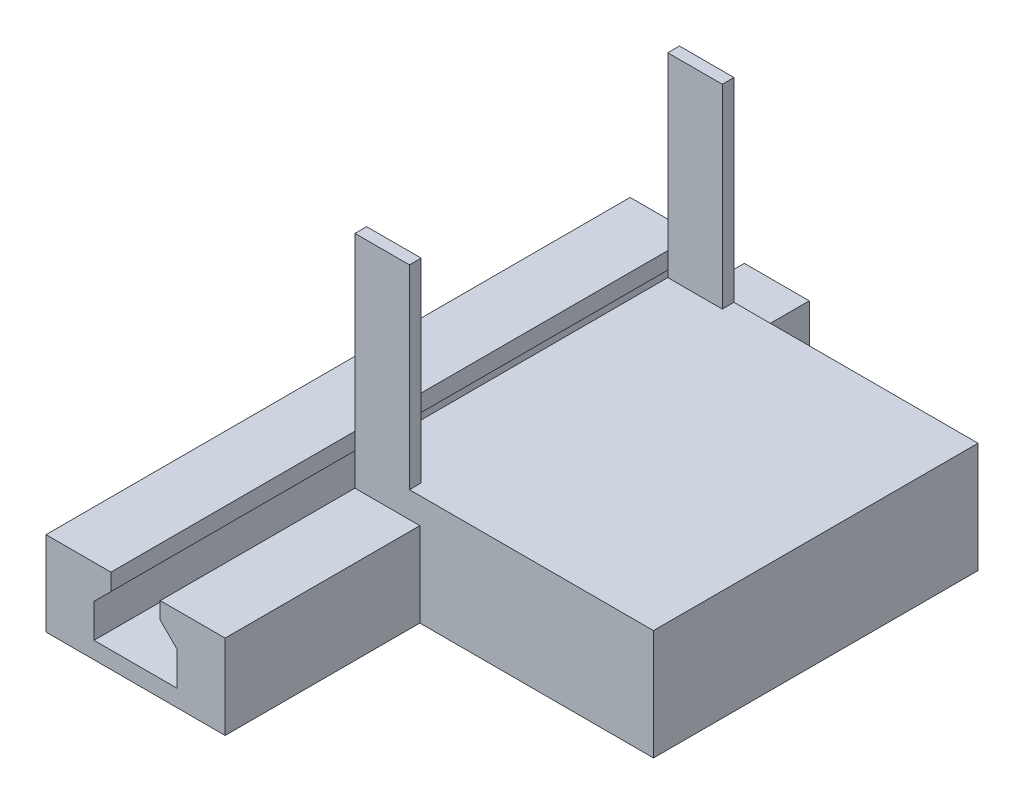
SolidWorks part; units mm, degrees
ref_plane "Plan de face" through (0, 0, 0) normal (0, 0, 1) x (1, 0, 0)
ref_plane "Plan de dessus" through (0, 0, 0) normal (0, 1, 0) x (1, 0, 0)
ref_plane "Plan de droite" through (0, 0, 0) normal (1, 0, 0) x (0, 0, -1)
sketch "Esquisse1" plane through (0, 0, 0) normal (0, 0, 1) x (1, 0, 0)
  line L0 (0, 0) -> (0, -5.2499) construction
  line L5 (0, 0) -> (0, 6.7252) construction
  line L6 (0, 0) -> (7.76, 0) construction
  line L7 (0, 0) -> (-6.4576, 0) construction
  line L8 (-3.2, 0) -> (3.2, 0)
  line L9 (-3.2, 0) -> (-3.2, 2.6)
  line L10 (3.2, 0) -> (3.2, 2.6)
  line L12 (-1.9, 5.2) -> (-1.9, 3.9)
  line L13 (1.9, 5.2) -> (1.9, 3.9)
  line L14 (-3.2, 2.6) -> (-1.9, 3.9)
  line L15 (1.9, 3.9) -> (3.2, 2.6)
  line L16 (-1.9, 5.2) -> (-6.9, 5.2)
  line L17 (-6.9, 5.2) -> (-6.9, -2.3)
  line L18 (-6.9, -2.3) -> (6.9, -2.3)
  line L19 (6.9, -2.3) -> (6.9, 5.2)
  line L20 (6.9, 5.2) -> (1.9, 5.2)
  point P10 (0, 0)
  point P15 (0, 5.2)
  dimension "D1" = 6.4
  dimension "D2" = 2.6
  dimension "D3" = 2.6
  dimension "D4" = 3.8
  dimension "D5" = 1.3
  dimension "D6" = 1.3
  dimension "D7" = 1.3
  dimension "D8" = 5
  dimension "D9" = 5
  dimension "D10" = 7.5
extrude "Boss.-Extru.1" add sketch "Esquisse1" along normal blind 45
sketch "Esquisse6" plane through (6.9, 0, 0) normal (1, 0, 0) x (0, 0, -1)
  line L0 (-45, -2.3) -> (0, -2.3) construction
  line L1 (-30, -2.3) -> (-5, -2.3)
  line L2 (-30, -2.3) -> (-30, 5.2)
  line L3 (-30, 5.2) -> (-5, 5.2)
  line L4 (-5, -2.3) -> (-5, 5.2)
  line L5 (-45, 5.2) -> (0, 5.2) construction
  line L6 (0, -2.3) -> (0, 5.2) construction
  dimension "D1" = 5
  dimension "D2" = 25
extrude "Boss.-Extru.6" add sketch "Esquisse6" along normal blind 18
sketch "Esquisse7" plane through (0, 5.2, 0) normal (0, 1, 0) x (1, 0, 0)
  line L0 (1.9, -45) -> (1.9, 0) construction
  line L1 (24.9, -30) -> (1.9, -30)
  line L2 (24.9, -30) -> (24.9, -5)
  line L3 (24.9, -5) -> (1.9, -5)
  line L4 (1.9, -30) -> (1.9, -5)
  dimension "D1" = 25
extrude "Boss.-Extru.7" add sketch "Esquisse7" along normal blind 2
sketch "Esquisse8" plane through (0, 7.2, 0) normal (0, 1, 0) x (1, 0, 0)
  line L1 (1.9, -30) -> (6.1, -30)
  line L2 (1.9, -30) -> (1.9, -29.1)
  line L3 (1.9, -29.1) -> (6.1, -29.1)
  line L4 (6.1, -30) -> (6.1, -29.1)
  line L5 (1.9, -5) -> (6.1, -5)
  line L6 (1.9, -5) -> (1.9, -5.9)
  line L7 (1.9, -5.9) -> (6.1, -5.9)
  line L8 (6.1, -5) -> (6.1, -5.9)
  dimension "D1" = 4.2
  dimension "D2" = 4.2
  dimension "D3" = 0.9
  dimension "D4" = 0.9
extrude "Boss.-Extru.8" add sketch "Esquisse8" along normal blind 20
sketch "Esquisse9" plane through (0, 27.2, 0) normal (0, 1, 0) x (1, 0, 0)
  line L1 (1.9, -5) -> (24.9, -5)
  line L2 (1.9, -5) -> (1.9, -30)
  line L3 (1.9, -30) -> (24.9, -30)
  line L4 (24.9, -5) -> (24.9, -30)
extrude "Boss.-Extru.9" add sketch "Esquisse9" against normal blind 5 and the other way blind 10
sketch "Esquisse10" plane through (24.9, 0, 0) normal (1, 0, 0) x (0, 0, -1)
  line L0 (-30, 37.2) -> (-5, 22.2) construction
  circle A0 centre (-17.5, 29.7) radius 4
  dimension "D1" = 8
extrude "Enlèv. mat.-Extru.1" cut sketch "Esquisse10" against normal through all
sketch "Esquisse12" plane through (0, 0, 30) normal (0, 0, 1) x (1, 0, 0)
  line L1 (24.9, 22.2) -> (1.9, 22.2)
  line L2 (24.9, 22.2) -> (24.9, 37.2)
  line L3 (24.9, 37.2) -> (1.9, 37.2)
  line L4 (1.9, 22.2) -> (1.9, 37.2)
extrude "Enlèv. mat.-Extru.2" cut sketch "Esquisse12" against normal through all
sketch "Esquisse13" plane through (0, 0, 30) normal (0, 0, 1) x (1, 0, 0)
  line L0 (24.9, 7.2) -> (24.9, -2.3) construction
  line L1 (-6.9, -2.3) -> (24.9, -2.3)
  line L2 (-6.9, -2.3) -> (-6.9, -1.3)
  line L3 (-6.9, -1.3) -> (24.9, -1.3)
  line L4 (24.9, -2.3) -> (24.9, -1.3)
  dimension "D1" = 1
extrude "Enlèv. mat.-Extru.3" cut sketch "Esquisse13" against normal through all both and the other way through all
